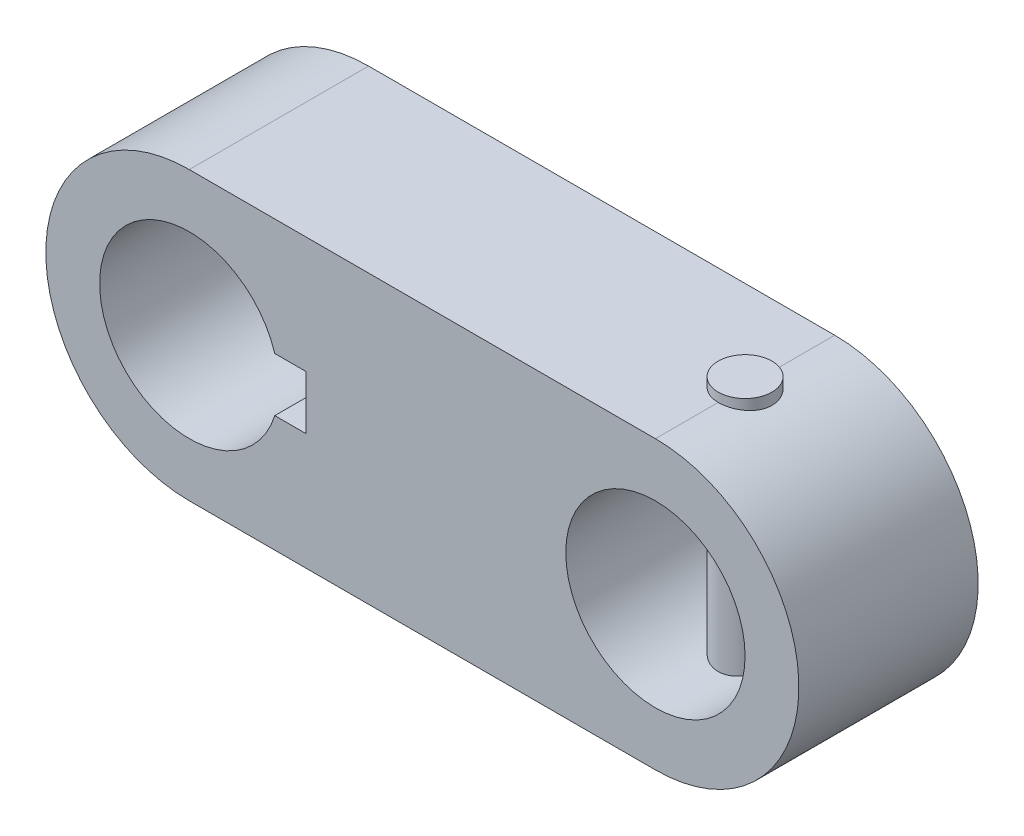
SolidWorks part; units mm, degrees
material "Plain Carbon Steel"
ref_plane "Front Plane" through (0, 0, 0) normal (0, 0, 1) x (1, 0, 0)
ref_plane "Top Plane" through (0, 0, 0) normal (0, 1, 0) x (1, 0, 0)
ref_plane "Right Plane" through (0, 0, 0) normal (1, 0, 0) x (0, 0, -1)
sketch "Sketch1" plane through (0, 0, 0) normal (0, 0, 1) x (1, 0, 0)
  line L0 (0, 0) -> (-18123.1894, 0) construction
  line L1 (0, 0) -> (0, 18123.1894) construction
  line L3 (13, 8) -> (-13, 8)
  line L5 (13, -8) -> (-13, -8)
  line L7 (13, 8) -> (-13, -8) construction
  line L8 (13, -8) -> (-13, 8) construction
  line L9 (-8.2303, 1.5) -> (-6.5, 1.5)
  line L11 (-8.2303, -1.5) -> (-6.5, -1.5)
  line L12 (-6.5, 1.5) -> (-6.5, -1.5)
  line L13 (-9.5, 1.5) -> (-6.5, -1.5) construction
  line L14 (-9.5, -1.5) -> (-6.5, 1.5) construction
  arc A0 (-13, -8) -> (-13, 8) centre (-13, 0) cw
  arc A1 (13, -8) -> (13, 8) centre (13, 0) ccw
  arc A2 (-8.2303, 1.5) -> (-8.2303, -1.5) centre (-13, 0) ccw
  circle A3 centre (13, 0) radius 5
  point P5 (0, 0)
  point P13 (-8, 0)
  point P19 (-6.5, 0)
  point P21 (-0.8055, -0.0345)
  dimension "D3" = 10
  dimension "D1" = 26
  dimension "D2" = 16
  dimension "D4" = 3
  dimension "1.5" = 1.5
extrude "Boss-Extrude1" add sketch "Sketch1" along normal mid plane 10
cosmetic thread "Cosmetic Thread1" parameters "D2"=12
sketch "Sketch2" plane through (0, 0, 0) normal (0, 1, 0) x (1, 0, 0)
  line L0 (0, 0) -> (50000, 0) construction
  line L1 (13, -5) -> (13, 5) construction
  circle A0 centre (13, 0) radius 1.5
  dimension "D1" = 3
extrude "Cut-Extrude1" cut sketch "Sketch2" against normal through all both and the other way through all
extrude "Boss-Extrude2" add sketch "Sketch2<2>" along normal mid plane 17 separate body
sketch "Sketch2<2>" plane through (0, 0, 0) normal (0, 1, 0) x (1, 0, 0) same geometry as "Sketch2"
